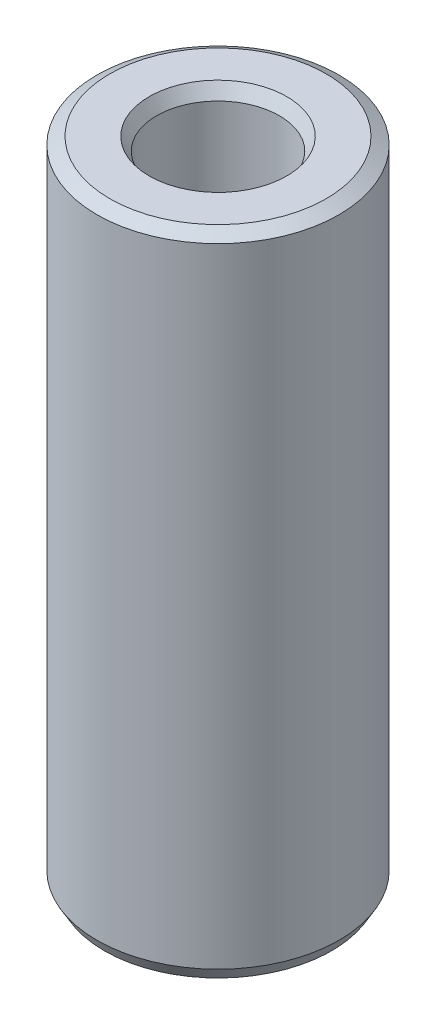
SolidWorks part; units mm, degrees
ref_plane "Front Plane" through (0, 0, 0) normal (0, 0, 1) x (1, 0, 0)
ref_plane "Top Plane" through (0, 0, 0) normal (0, 1, 0) x (1, 0, 0)
ref_plane "Right Plane" through (0, 0, 0) normal (1, 0, 0) x (0, 0, -1)
sketch "Sketch1" plane through (0, 0, 0) normal (0, 1, 0) x (1, 0, 0)
  circle A0 centre (0, 0) radius 47.5
  dimension "SLEEVE_OD" = 95
extrude "Boss-Extrude1" add sketch "Sketch1" along normal blind 254.5039
sketch "Sketch2" plane through (0, 0, 0) normal (0, 1, 0) x (1, 0, 0)
  circle A0 centre (0, 0) radius 24.0822
  dimension "BORE_D" = 48.1643
extrude "Cut-Extrude1" cut sketch "Sketch2" along normal through all
chamfer "Chamfer1" distance 2.9112 angle 60 4 edges at (0, 254.5039, 24.0822) (0, 0, 24.0822) (0, 0, 47.5) (0, 254.5039, 47.5) first distance on face at (0, 254.5039, 24.0822) first distance on face at (0, 0, 24.0822) first distance on face at (0, 254.5039, 47.5)
